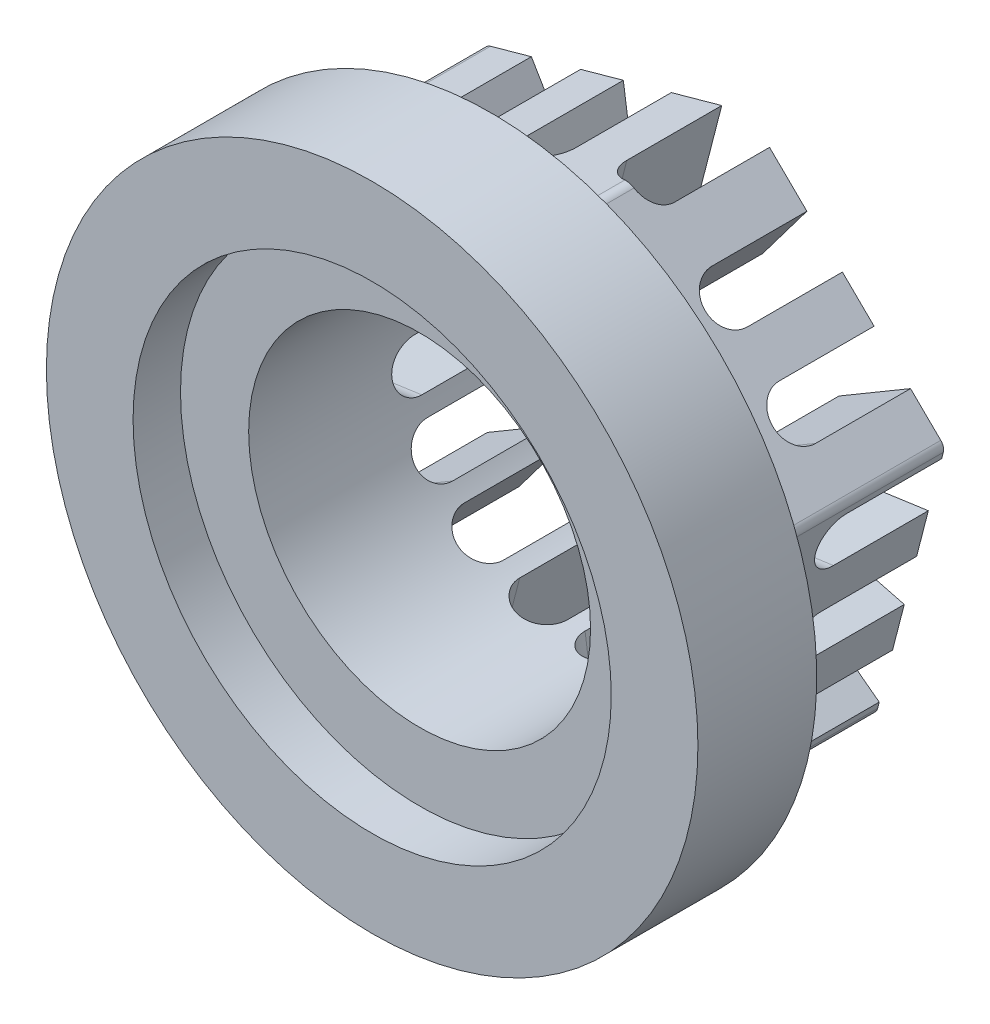
SolidWorks part; units mm, degrees
material "AISI Type 316L stainless steel"
ref_plane "Front Plane" through (0, 0, 0) normal (0, 0, 1) x (1, 0, 0)
ref_plane "Top Plane" through (0, 0, 0) normal (0, 1, 0) x (1, 0, 0)
ref_plane "Right Plane" through (0, 0, 0) normal (1, 0, 0) x (0, 0, -1)
sketch "Sketch1" plane through (0, 0, 0) normal (0, 0, 1) x (1, 0, 0)
  circle A0 centre (0, 0) radius 21.7995
  dimension "D1" = 43.5991
extrude "Boss-Extrude1" add sketch "Sketch1" along normal blind 20.6502
sketch "Sketch2" plane through (0, 0, 20.6502) normal (0, 0, 1) x (1, 0, 0)
  circle A0 centre (0, 0) radius 11.4402
  dimension "D1" = 22.8803
extrude "Cut-Extrude1" cut sketch "Sketch2" against normal blind 20.6502
sketch "Sketch3" plane through (0, 0, 20.6502) normal (0, 0, 1) x (1, 0, 0)
  circle A0 centre (0, 0) radius 16
  dimension "D1" = 32
extrude "Cut-Extrude2" cut sketch "Sketch3" against normal blind 3.175
sketch "Sketch4" plane through (0, 0, 0) normal (0, 0, -1) x (-1, 0, 0)
  line L1 (17.6618, -4.9073) -> (13.0808, 12.8419)
  line L2 (13.0808, 12.8419) -> (-4.581, 17.7492)
  line L3 (-4.581, 17.7492) -> (-17.6618, 4.9073)
  line L4 (-17.6618, 4.9073) -> (-13.0808, -12.8419)
  line L5 (-13.0808, -12.8419) -> (4.581, -17.7492)
  line L6 (4.581, -17.7492) -> (17.6618, -4.9073)
  circle A1 centre (0, 0) radius 15.875 construction
  dimension "D1" = 31.75
extrude "Cut-Extrude3" cut sketch "Sketch4" against normal blind 12.7 flip side to cut
sketch "Sketch5" plane through (-15.3713, 3.9673, 0) normal (-0.9683, 0.2499, 0) x (0, 0, 1)
  line L0 (0, 0) -> (12.7, 0) construction
  line L1 (12.7, -9.1654) -> (12.7, 9.1654) construction
  line L2 (6.35, 1.651) -> (0, 1.651)
  line L3 (0, -9.1654) -> (0, 9.1654) construction
  line L4 (0, 1.651) -> (0, -1.651)
  line L5 (0, -1.651) -> (6.35, -1.651)
  arc A1 (6.35, 1.651) -> (6.35, -1.651) centre (6.35, 0) cw
  point P6 (3.175, -1.651)
  dimension "D1" = 3.302
extrude "Cut-Extrude4" cut sketch "Sketch5" against normal blind 9.8552 and the other way blind 9.8552
pattern_circular "CirPattern1" count 16 over 360 about axis through (0, 0, 17.4752) along (0, 0, 1) of "Cut-Extrude4" reverse direction yes
fillet "Fillet1" radius 0.635 6 edges at (-17.6618, -4.9073, 6.35) (-13.0808, 12.8419, 6.35) (4.581, 17.7492, 10.3505) (17.6618, 4.9073, 6.35) (13.0808, -12.8419, 6.35) (-4.581, -17.7492, 10.3505)
ref_axis "Axis1" through (0, 0, 17.4752) along (0, 0, 1)
